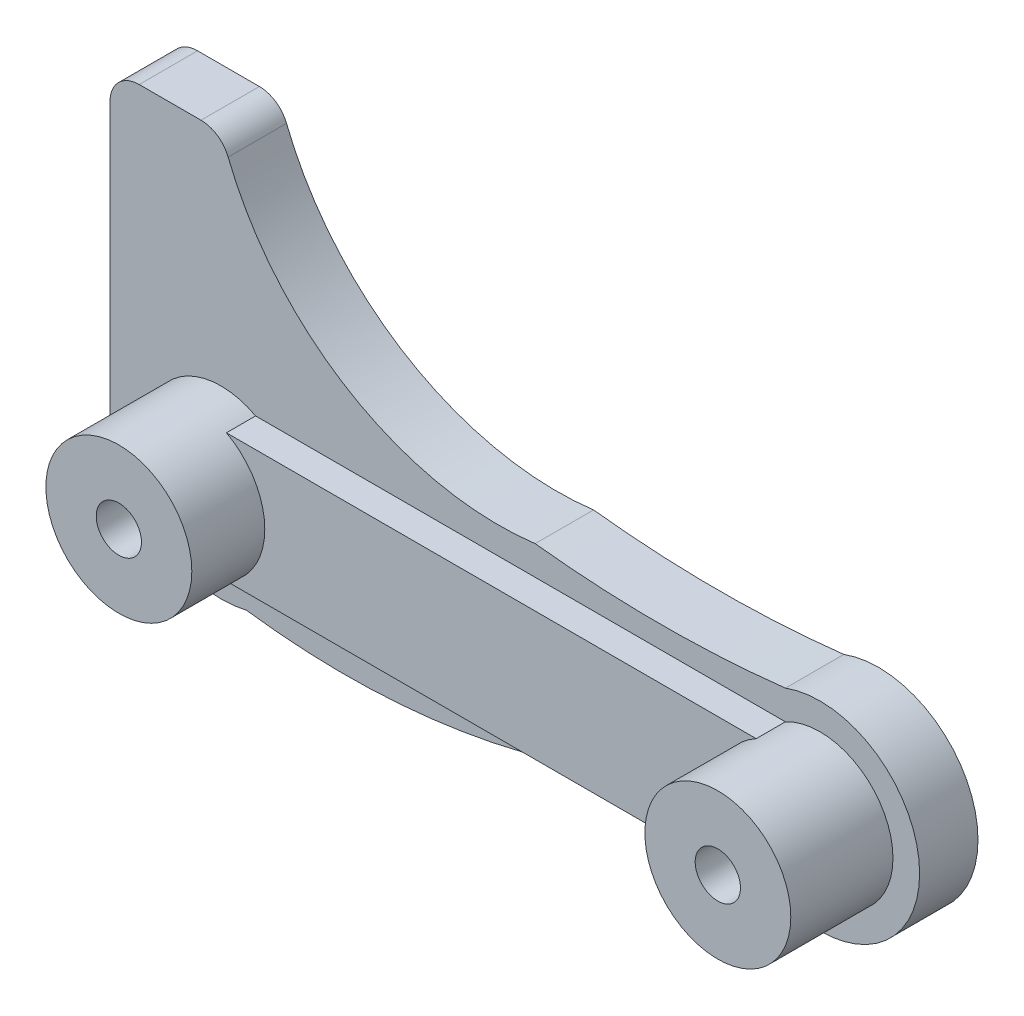
SolidWorks part; units mm, degrees
ref_plane "Plan de face" through (0, 0, 0) normal (0, 0, 1) x (1, 0, 0)
ref_plane "Plan de dessus" through (0, 0, 0) normal (0, 1, 0) x (1, 0, 0)
ref_plane "Plan de droite" through (0, 0, 0) normal (1, 0, 0) x (0, 0, -1)
sketch "Esquisse1" plane through (0, 0, 0) normal (0, 0, 1) x (1, 0, 0)
  line L0 (2.3705, 4.4023) -> (38.6705, 4.4023)
  line L1 (14.9398, 0) -> (50014.9398, 0) construction
  line L2 (2.3705, -4.4023) -> (38.6705, -4.4023)
  arc A1 (2.3705, 4.4023) -> (2.3705, -4.4023) centre (0, 0) ccw
  arc A2 (38.6705, -4.4023) -> (38.6705, 4.4023) centre (41.0411, 0) ccw
  dimension "D1" = 10
  dimension "D2" = 10
  dimension "D3" = 36.3
extrude "Boss.-Extru.1" add sketch "Esquisse1" along normal blind 3 and the other way blind 3
sketch "Esquisse2" plane through (0, 0, 3) normal (0, 0, 1) x (1, 0, 0)
  line L0 (0, 0) -> (50000, 0) construction
  circle A0 centre (0, 0) radius 1.55
  circle A2 centre (41.0411, 0) radius 1.55
  arc A3 (38.6705, -4.4023) -> (38.6705, 4.4023) centre (41.0411, 0) ccw construction
  dimension "D1" = 3.1
  dimension "D2" = 3.1
extrude "Enlèv. mat.-Extru.1" cut sketch "Esquisse2" along direction (0, 0, 1) on the side against the normal up to surface (6 mm away) contours A0 | A2 L0 | L0 A2 | L0 A0 region at (41.0411, 0.6578, 3) region at (41.0411, -0.6578, 3) region at (-1.5062, 0, 3) up to face at (20.5205, 0, -3)
sketch "Sketch1" plane through (0, 0, 3) normal (0, 0, 1) x (1, 0, 0)
  circle A0 centre (0, 0) radius 5
  circle A1 centre (0, 0) radius 1.55
  circle A2 centre (41.0411, 0) radius 1.55
  circle A3 centre (41.0411, 0) radius 5
  arc A6 (38.6705, -4.4023) -> (38.6705, 4.4023) centre (41.0411, 0) ccw construction
  arc A7 (2.3705, 4.4023) -> (2.3705, -4.4023) centre (0, 0) ccw construction
extrude "Boss-Extrude1" add sketch "Sketch1" along normal blind 5
ref_plane "Plane1" through (2.3705, 0, 0) normal (1, 0, 0) x (0, 0, -1)
sketch "Sketch3" plane through (0, 0, -3) normal (0, 0, -1) x (-1, 0, 0)
  line L0 (-38.6705, 4.4023) -> (-2.3705, 4.4023)
  line L1 (-38.6705, -4.4023) -> (-2.3705, -4.4023)
  line L2 (-38.6705, 6.4023) -> (49961.3295, 6.4023) construction
  line L3 (-38.6705, 4.4023) -> (-38.6705, 50004.4023) construction
  line L4 (-0.0363, 20.0804) -> (7.6043, 20.0804)
  line L5 (7.6043, 20.0804) -> (7.6043, -0.7845)
  line L6 (-46.1731, -6.4023) -> (49953.8269, -6.4023) construction
  arc A0 (-38.6705, 4.4023) -> (-38.6705, -4.4023) centre (-41.0411, 0) ccw
  arc A1 (-2.3705, 4.4023) -> (-2.3705, -4.4023) centre (0, 0) cw
  arc A2 (-38.6705, 6.4023) -> (-38.6705, -6.4023) centre (-41.0411, 0) ccw
  arc A3 (-38.6705, 6.4023) -> (-21.5269, 6.4023) centre (-30.0987, 81.2104) ccw
  arc A4 (-21.5269, 6.4023) -> (-0.0363, 20.0804) centre (-19.0311, 26.2028) ccw
  arc A5 (7.6043, -0.7845) -> (-1.7434, -7.4433) centre (0, 0) cw
  arc A6 (-38.6705, -6.4023) -> (-20.6429, -6.4023) centre (-29.6567, -67.5907) cw
  arc A7 (-20.6429, -6.4023) -> (-1.7434, -7.4433) centre (-8.4653, 42.6068) ccw
  dimension "D1" = 2
  dimension "D2" = 2
extrude "Boss-Extrude3" add sketch "Sketch3" against normal blind 4
fillet "Fillet1" radius 2 2 edges at (-7.6043, 20.0804, -1) (0.0363, 20.0804, -1)
